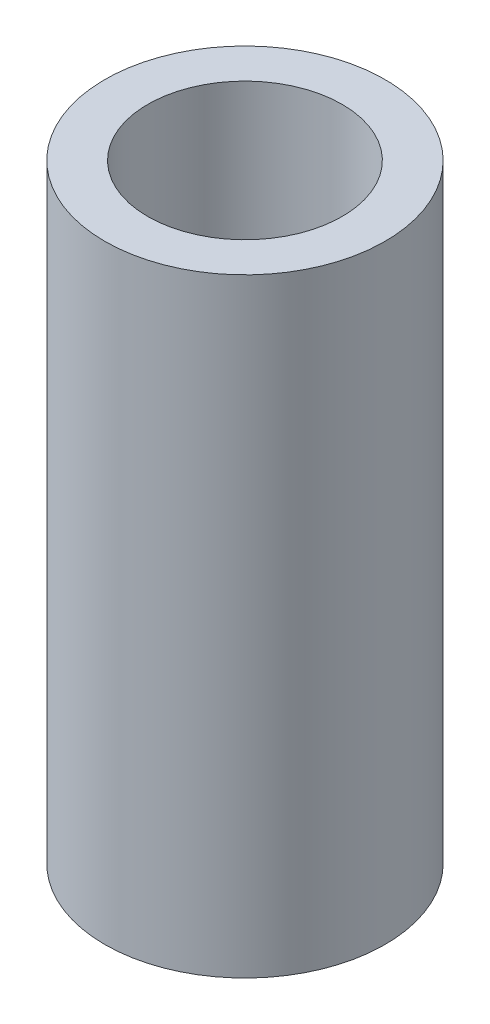
SolidWorks part; units mm, degrees
ref_plane "Front Plane" through (0, 0, 0) normal (0, 0, 1) x (1, 0, 0)
ref_plane "Top Plane" through (0, 0, 0) normal (0, 1, 0) x (1, 0, 0)
ref_plane "Right Plane" through (0, 0, 0) normal (1, 0, 0) x (0, 0, -1)
sketch "Sketch1" plane through (0, 0, 0) normal (0, 1, 0) x (1, 0, 0)
  circle A0 centre (0, 0) radius 17.5
  dimension "SLEEVE_OD" = 35
extrude "Boss-Extrude1" add sketch "Sketch1" along normal blind 76.0452
sketch "Sketch2" plane through (0, 0, 0) normal (0, 1, 0) x (1, 0, 0)
  circle A0 centre (0, 0) radius 12.1366
  dimension "BORE_D" = 24.2732
extrude "Cut-Extrude1" cut sketch "Sketch2" along normal through all
chamfer "Chamfer1" distance 3.0659 angle 45 rebuild error yes
